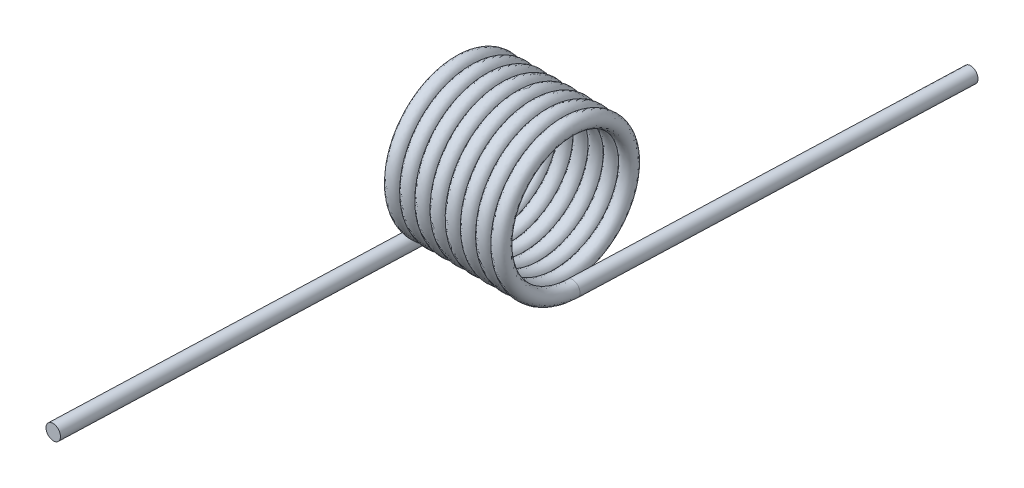
SolidWorks part; units mm, degrees
ref_plane "Front" through (0, 0, 0) normal (0, 0, 1) x (1, 0, 0)
ref_plane "Top" through (0, 0, 0) normal (0, 1, 0) x (1, 0, 0)
ref_plane "Right" through (0, 0, 0) normal (1, 0, 0) x (0, 0, -1)
sketch "Sketch1" plane through (0, 0, 0) normal (1, 0, 0) x (0, 0, -1)
  line L0 (0, 0) -> (0, -7.9375) construction
  line L1 (0, -7.9375) -> (0, -8.9281) construction
  line L2 (0, -8.9281) -> (0, -9.9187) construction
  circle A0 centre (0, 0) radius 7.9375 construction
  circle A1 centre (0, 0) radius 9.9187 construction
  circle A2 centre (0, 0) radius 8.9281
  circle A3 centre (0, -8.9281) radius 0.9906 construction
  circle A4 centre (0, 0) radius 6.35 construction
  dimension "Wire Dia" = 1.9812
  dimension "Spring OD" = 19.8374
  dimension "Max Rod OD" = 12.7
curve "Helix/Spiral1" pitch 2.0066 height 16.0528 radius 8.9281 centre (0, 0, 0) axis (1, 0, 0) start towards (0, 0, -1)
ref_plane "Plane1" through (0, -8.9281, 0) normal (0.0357, 0, -0.9994) x (-0.9994, 0, -0.0357)
sketch "Sketch2" plane through (0, -8.9281, 0) normal (0.0357, 0, -0.9994) x (-0.9994, 0, -0.0357)
  circle A0 centre (0, 0) radius 0.9906
  dimension "D1" = 1.9812
sweep "Sweep1" add profiles "Sketch2" path "Helix/Spiral1"
sketch "Sketch3" plane through (0, 0, 0) normal (-0.0357, 0, 0.9994) x (0.9994, 0, 0.0357)
  circle A1 centre (0, -8.9281) radius 0.9906
  circle A2 centre (0, -8.9281) radius 0.9906
  dimension "D1" = 0
extrude "Extrude1" add sketch "Sketch3" along normal blind 50.8
sketch "Sketch4" plane through (0.0205, 0, -0.5735) normal (0.0357, 0, -0.9994) x (-0.9957, -0.0856, -0.0356)
  circle A1 centre (-15.2194, -10.2686) radius 0.9906
  circle A2 centre (-15.2194, -10.2686) radius 0.9906
  dimension "D1" = 0
extrude "Extrude2" add sketch "Sketch4" along normal blind 50.8
sketch "Sketch5" plane through (0, 0, 0) normal (1, 0, 0) x (0, 0, -1)
  circle A0 centre (0, 0) radius 6.35 construction
  circle A1 centre (0, 0) radius 6.35
equation "\"D4@Helix/Spiral1\"=\"Wire Dia@Sketch1\"+.001"
equation "\"D1@Sketch2\"=\"Wire Dia@Sketch1\""
equation "\"D1@Extrude2\"=\"Leg Length@Extrude1\""
